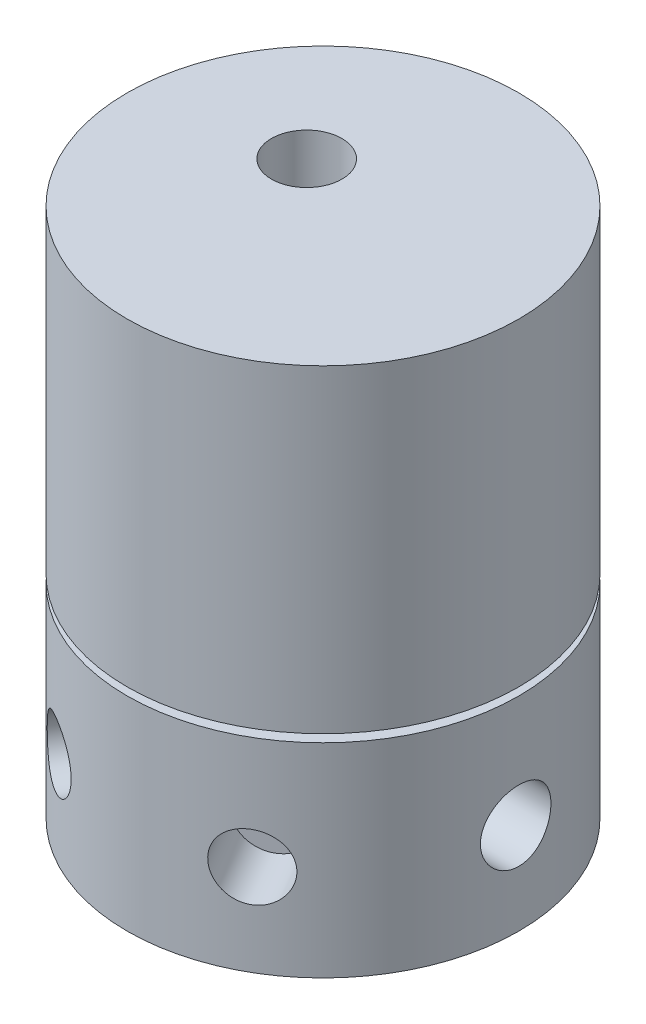
SolidWorks part; units mm, degrees
material "Brass"
ref_plane "Front Plane" through (0, 0, 0) normal (0, 0, 1) x (1, 0, 0)
ref_plane "Top Plane" through (0, 0, 0) normal (0, 1, 0) x (1, 0, 0)
ref_plane "Right Plane" through (0, 0, 0) normal (1, 0, 0) x (0, 0, -1)
sketch "Sketch1" plane through (0, 0, 0) normal (0, 1, 0) x (1, 0, 0)
  circle A0 centre (0, 0) radius 38.1
  dimension "D1" = 76.2
extrude "Boss-Extrude1" add sketch "Sketch1" along normal blind 39.624
sketch "Sketch2" plane through (0, 39.624, 0) normal (0, 1, 0) x (1, 0, 0)
  circle A0 centre (0, 0) radius 22.606
  dimension "D1" = 45.212
extrude "Boss-Extrude2" add sketch "Sketch2" along normal blind 12.7
ref_plane "Plane1" through (0, 41.148, 0) normal (0, 1, 0) x (1, 0, 0)
sketch "Sketch3" plane through (0, 41.148, 0) normal (0, 1, 0) x (1, 0, 0)
  circle A0 centre (0, 0) radius 38.1
  dimension "D1" = 76.2
extrude "Boss-Extrude3" add sketch "Sketch3" along normal blind 61.976
sketch "Sketch4" plane through (0, 0, 0) normal (1, 0, 0) x (0, 0, -1)
  line L0 (0, 0) -> (0, 17.78) construction
  circle A0 centre (0, 17.78) radius 6.858
  dimension "D2" = 13.716
  dimension "D1" = 17.78
extrude "Cut-Extrude1" cut sketch "Sketch4" along normal blind 12.7 from offset 25.4
sketch "Sketch5" plane through (0, 0, 0) normal (1, 0, 0) x (0, 0, -1)
  line L0 (0, 0) -> (0, 17.78) construction
  circle A0 centre (0, 17.78) radius 9.525
  dimension "D2" = 19.05
  dimension "D1" = 17.78
extrude "Cut-Extrude2" cut sketch "Sketch5" against normal blind 12.7 from offset 25.4 offset against normal yes
sketch "Sketch6" plane through (0, 0, 0) normal (0, -1, 0) x (1, 0, 0)
  line L0 (0, 38.1) -> (0, -38.1) construction
  line L1 (0, 0) -> (19.05, 32.9956) construction
  line L2 (0, 0) -> (-19.05, 32.9956) construction
  circle A0 centre (0, 0) radius 38.1 construction
  point P6 (0, 0)
  dimension "D1" = 76.2
  dimension "D2" = 30
  dimension "D3" = 30
ref_plane "Plane3" through (-19.05, 0, 32.9956) normal (-0.5, 0, 0.866) x (0.866, 0, 0.5)
sketch "Sketch7" plane through (-19.05, 0, 32.9956) normal (-0.5, 0, 0.866) x (0.866, 0, 0.5)
  line L0 (0, 0) -> (0, 17.78) construction
  circle A0 centre (0, 17.78) radius 6.35
  dimension "D2" = 12.7
  dimension "D1" = 17.78
extrude "Cut-Extrude3" cut sketch "Sketch7" against normal blind 12.7
ref_plane "Plane4" through (19.05, 0, 32.9956) normal (0.5, 0, 0.866) x (0.866, 0, -0.5)
sketch "Sketch8" plane through (19.05, 0, 32.9956) normal (0.5, 0, 0.866) x (0.866, 0, -0.5)
  line L0 (0, 0) -> (0, 17.78) construction
  circle A0 centre (0, 17.78) radius 6.35
  dimension "D2" = 12.7
  dimension "D1" = 17.78
extrude "Cut-Extrude5" cut sketch "Sketch8" against normal blind 12.7
sketch "Sketch9" plane through (0, 103.124, 0) normal (0, 1, 0) x (1, 0, 0)
  line L0 (0, 38.1) -> (0, -38.1) construction
  line L2 (0, 0) -> (-9.525, 0) construction
  line L3 (-9.525, 0) -> (-9.525, 6.35) construction
  circle A0 centre (-9.525, 6.35) radius 6.858
  point P4 (0, 0)
  dimension "D3" = 13.716
  dimension "D1" = 9.525
  dimension "D2" = 6.35
extrude "Cut-Extrude6" cut sketch "Sketch9" against normal blind 12.7
